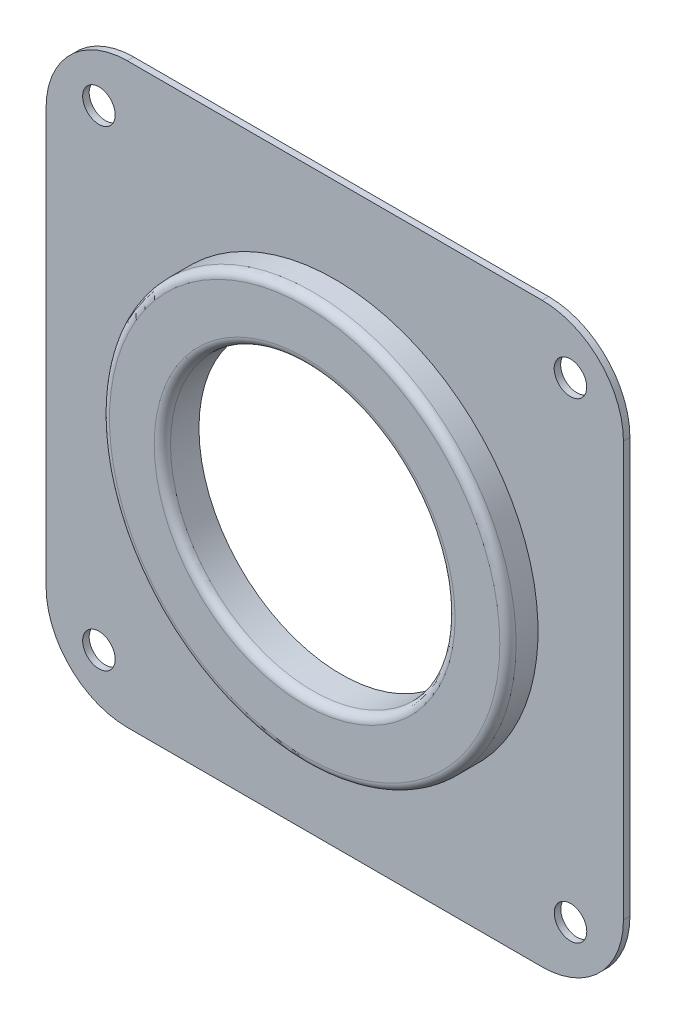
SolidWorks part; units mm, degrees
ref_plane "前视基准面" through (0, 0, 0) normal (0, 0, 1) x (1, 0, 0)
ref_plane "上视基准面" through (0, 0, 0) normal (0, 1, 0) x (1, 0, 0)
ref_plane "右视基准面" through (0, 0, 0) normal (1, 0, 0) x (0, 0, -1)
ref_plane "基准面1" through (0, 0, 1) normal (0, 0, 1) x (1, 0, 0)
sketch "草图1" plane through (0, 0, 1) normal (0, 0, 1) x (1, 0, 0)
  line L0 (-35.5, 35.5) -> (-35.5, -35.5)
  line L1 (-35.5, -35.5) -> (35.5, -35.5)
  line L2 (35.5, -35.5) -> (35.5, 35.5)
  line L3 (35.5, 35.5) -> (-35.5, 35.5)
extrude "凸台-拉伸1" add sketch "草图1" against normal blind 0.8
ref_plane "基准面2" through (0, 0, 0) normal (0, -1, 0) x (1, 0, 0)
sketch "草图2" plane through (0, 0, 0) normal (0, -1, 0) x (1, 0, 0)
  line L0 (25, 4.7) -> (0, 4.7)
  line L1 (0, 4.7) -> (0, 1)
  line L2 (0, 1) -> (25, 1)
  line L3 (25, 1) -> (25, 4.7)
  line L4 (0, 4.7) -> (0, 1) construction
  dimension "D1" = 3.7
revolve "旋转1" add sketch "草图2" angle 360 about L4 reverse direction yes
hole_wizard "M30 间隙孔1" positions "草图4" profile "草图3" hole size "M30" standard "ANSI Metric"
sketch "草图4" plane through (0, 0, 4.7) normal (0, 0, 1) x (1, 0, 0)
  point P0 (0, 0)
sketch "草图3" plane through (0, 0, 4.7) normal (1, 0, 0) x (0, -1, 0)
  line L0 (0, 0) -> (0, 4.5)
  line L1 (0, 4.5) -> (17.5, 4.5)
  line L2 (17.5, 4.5) -> (17.5, 0)
  line L5 (17.5, 0) -> (0, 0)
  line L11 (0, -6.35) -> (0, 107.95) construction
  dimension "通孔孔直径" = 35
  dimension "通孔孔深度" = 4.5
hole_wizard "Ø4.0 (4) 直径孔1" positions "草图6" profile "草图5" hole size "Ø4.0" standard "ANSI Metric" end condition through all
sketch "草图6" plane through (0, 0, 1) normal (0, 0, 1) x (1, 0, 0)
  point P0 (-29, 28.98)
  point P1 (-29, -29)
  point P2 (28.9928, -28.9928)
  point P3 (28.9828, 28.9828)
  dimension "D1" = 82
  dimension "D2" = 82
sketch "草图5" plane through (-29, 28.98, 1) normal (1, 0, 0) x (0, -1, 0)
  line L0 (0, 0) -> (0, 0.8)
  line L1 (0, 0.8) -> (2, 0.8)
  line L2 (2, 0.8) -> (2, 0)
  line L5 (2, 0) -> (0, 0)
  line L11 (0, -6.35) -> (0, 107.95) construction
  dimension "通孔孔直径" = 4
  dimension "通孔孔深度" = 0.8
fillet "圆角1" radius 1 2 edges at (17.5, 0, 4.7) (-25, 0, 4.7) tangent propagation no
fillet "圆角2" radius 10 4 edges at (35.5, -35.5, 0.6) (-35.5, -35.5, 0.6) (-35.5, 35.5, 0.6) (35.5, 35.5, 0.6) tangent propagation no
